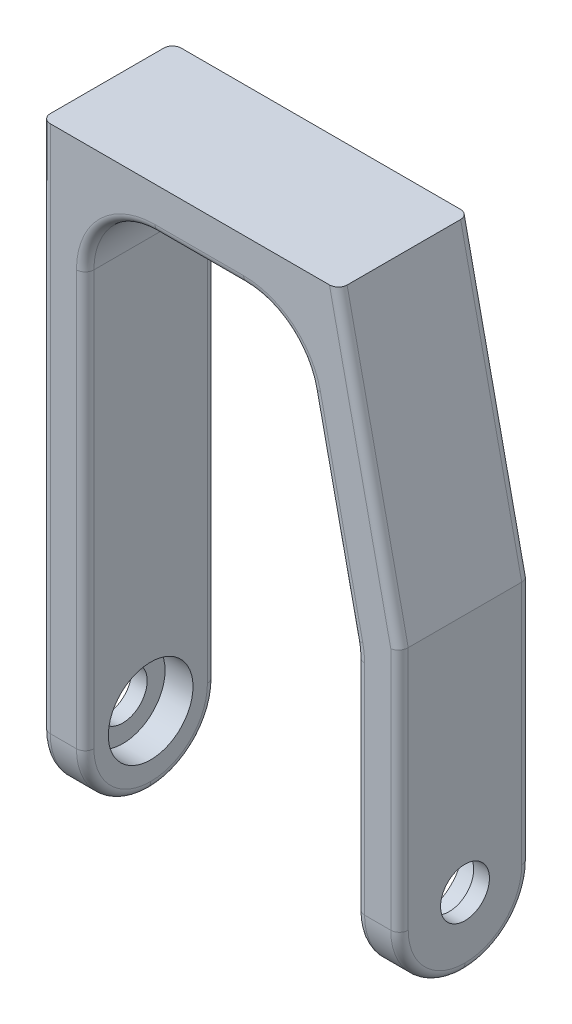
SolidWorks part; units mm, degrees
ref_plane "前视基准面" through (0, 0, 0) normal (0, 0, 1) x (1, 0, 0)
ref_plane "上视基准面" through (0, 0, 0) normal (0, 1, 0) x (1, 0, 0)
ref_plane "右视基准面" through (0, 0, 0) normal (1, 0, 0) x (0, 0, -1)
sketch "草图1" plane through (0, 0, 0) normal (0, 1, 0) x (1, 0, 0)
  line L1 (24, 7.5) -> (-17, 7.5)
  line L2 (24, 7.5) -> (24, -7.5)
  line L3 (24, -7.5) -> (-17, -7.5)
  line L4 (-17, 7.5) -> (-17, -7.5)
  line L5 (24, 7.5) -> (-17, -7.5) construction
  line L6 (24, -7.5) -> (-17, 7.5) construction
  point P0 (0, 0)
  point P6 (0, 0)
  point P7 (0, 0)
  point P8 (0, 0)
  point P9 (0, 0)
  point P10 (0, 0)
  point P11 (0, 0)
  point P12 (0, 0)
  point P13 (0, 0)
  point P14 (0, 0)
  point P15 (0, 0)
  point P16 (0, 0)
extrude "凸台-拉伸1" add sketch "草图1" against normal blind 68
sketch "草图3" plane through (0, 0, 7.5) normal (0, 0, 1) x (1, 0, 0)
  line L0 (-17, -68) -> (24, -68) construction
  line L1 (-12, -68) -> (19, -68)
  line L2 (-12, -68) -> (-12, -5)
  line L3 (-12, -5) -> (12.6087, -5)
  line L4 (19, -68) -> (19, -34.6453)
  line L5 (12.6087, -5) -> (19, -34.6453)
  line L6 (17, 0) -> (27.4891, -48.6528)
  line L7 (17, 0) -> (27.4891, 0)
  line L8 (27.4891, 0) -> (27.4891, -48.6528)
  line L9 (-17, 0) -> (24, 0) construction
  line L10 (-17, 0) -> (24, 0) construction
  point P1 (27.4891, -52.7043)
  point P7 (27.4891, 10.2005)
  point P8 (15.7611, 0)
  point P13 (0, 0)
  point P14 (0, 0)
  point P17 (27.4891, -48.6528)
extrude "切除-拉伸1" cut sketch "草图3" against normal through all
fillet "圆角1" radius 8 3 edges at (-12, -5, 0) (19, -34.6453, 0) (12.6087, -5, 0)
fillet "圆角3" radius 7.5 4 edges at (21.5, -68, -7.5) (21.5, -68, 7.5) (-14.5, -68, -7.5) (-14.5, -68, 7.5)
fillet "圆角2" radius 1 28 edges at (-17, -30.25, -7.5) (24, -46.4844, -7.5) (24, -46.4844, 7.5) (-17, -30.25, 7.5) (-9.6569, -7.3431, 7.5) (1.0748, -5, 7.5) (19, -47.9989, 7.5) (19, -47.9989, -7.5) (1.0748, -5, -7.5) (-9.6569, -7.3431, -7.5) (-12, -36.75, -7.5) (-12, -36.75, 7.5) (19, -65.8033, 5.3033) (19, -65.8033, -5.3033) (-12, -65.8033, -5.3033) (-12, -65.8033, 5.3033) (-17, -65.8033, 5.3033) (-17, -65.8033, -5.3033) (24, -65.8033, -5.3033) (24, -65.8033, 5.3033) (11.1752, -6.7755, 7.5) (16.3951, -22.5629, 7.5) (18.955, -34.6501, 7.5) (18.955, -34.6501, -7.5) (16.3951, -22.5629, -7.5) (11.1752, -6.7755, -7.5) (20.5, -16.2344, -7.5) (20.5, -16.2344, 7.5)
sketch "草图4" plane through (24, 0, 0) normal (1, 0, 0) x (0, 0, -1)
  circle A0 centre (0, -60) radius 2.8
extrude "切除-拉伸2" cut sketch "草图4" against normal through all
sketch "草图6" plane through (19, 0, 0) normal (1, 0, 0) x (0, 0, -1)
  circle A0 centre (0, -60) radius 4.85
extrude "切除-拉伸4" cut sketch "草图6" along normal blind 3.2
ref_plane "基准面1" through (3.5, 0, 0) normal (1, 0, 0) x (0, 0, -1)
mirror "镜向2" about plane through (3.5, 0, 0) normal (1, 0, 0) of "切除-拉伸4"
sketch "草图7" plane through (0, 0, 0) normal (1, 0, 0) x (0, 0, -1)
  line L1 (-20.1249, 0) -> (22.9708, 0)
  line L2 (-20.1249, 0) -> (-20.1249, 43.9552)
  line L3 (-20.1249, 43.9552) -> (22.9708, 43.9552)
  line L4 (22.9708, 0) -> (22.9708, 43.9552)
  circle A0 centre (0, 19.0057) radius 12.4
